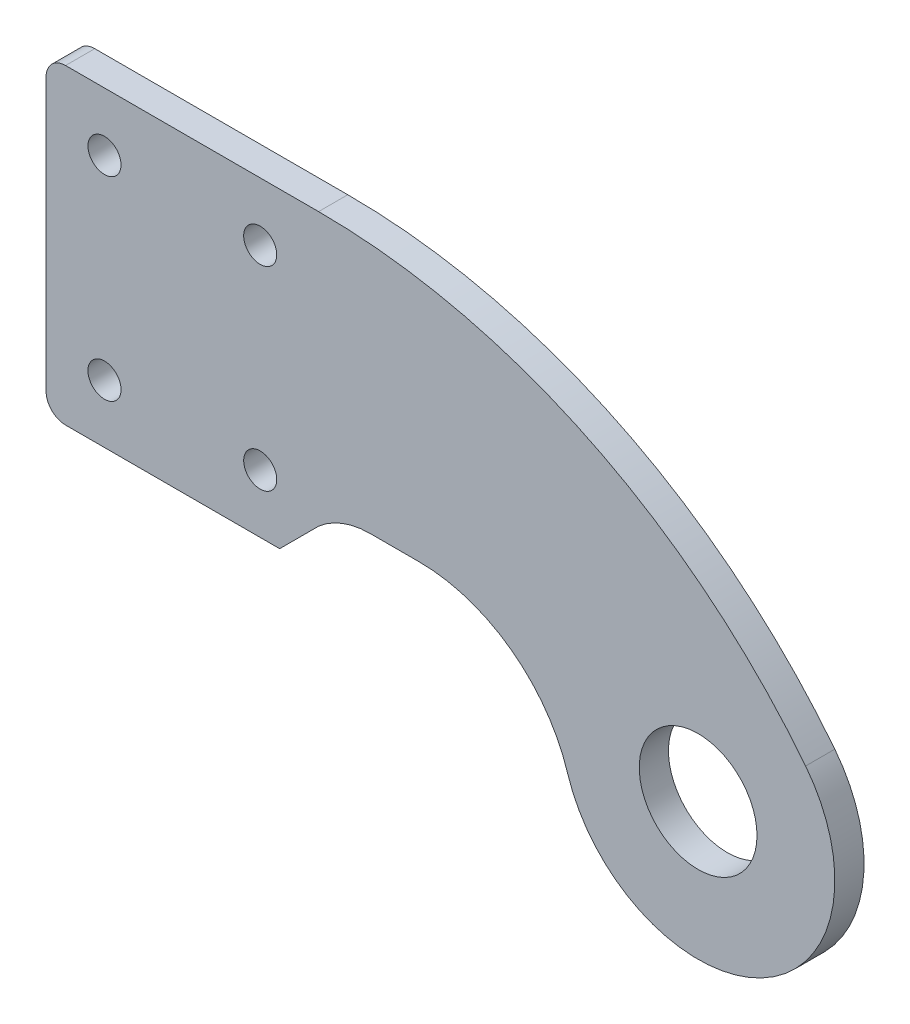
SolidWorks part; units mm, degrees
material "Hexcel AS4C (3000 Filaments)"
ref_plane "Plan de face" through (0, 0, 0) normal (0, 0, 1) x (1, 0, 0)
ref_plane "Plan de dessus" through (0, 0, 0) normal (0, 1, 0) x (1, 0, 0)
ref_plane "Plan de droite" through (0, 0, 0) normal (1, 0, 0) x (0, 0, -1)
sketch "Esquisse1" plane through (0, 0, 0) normal (0, 0, 1) x (1, 0, 0)
  line L0 (-19.5, 16.5) -> (2.8879, 6.4039) construction
  line L1 (-30.5, 13.5) -> (-22.5, 13.5) construction
  line L2 (-30.5, 13.5) -> (-30.5, 3.5) construction
  line L3 (-30.5, 3.5) -> (-22.5, 3.5) construction
  line L4 (-22.5, 13.5) -> (-22.5, 3.5) construction
  line L5 (-33.5, 16.5) -> (-19.5, 16.5)
  line L6 (-33.5, 16.5) -> (-33.5, 0.5)
  line L7 (-33.5, 0.5) -> (-19.5, 0.5)
  line L8 (-19.5, 16.5) -> (-19.5, 0.5) construction
  line L9 (-19.5, 0.5) -> (-19.5, 4.475) construction
  line L10 (-19.5, 4.475) -> (-5.4153, 4.475) construction
  line L11 (-19.5, 0.5) -> (-7.0072, 0.5)
  circle A0 centre (0, 0) radius 3.025
  circle A1 centre (0, 0) radius 7.025 construction
  circle A2 centre (-30.5, 13.5) radius 0.85
  circle A3 centre (-22.5, 13.5) radius 0.85
  circle A4 centre (-22.5, 3.5) radius 0.85
  circle A5 centre (-30.5, 3.5) radius 0.85
  arc A6 (-5.4153, 4.475) -> (2.8879, 6.4039) centre (0, 0) ccw construction
  arc A7 (-7.0072, 0.5) -> (5.5229, 4.3414) centre (0, 0) ccw
  arc A8 (-19.5, 16.5) -> (5.5229, 4.3414) centre (-19.5, -15.3285) cw
  dimension "D1" = 8
  dimension "D8" = 14.05
  dimension "D9" = 6.05
  dimension "D10" = 1.7
  dimension "D11" = 1.7
  dimension "D12" = 1.7
  dimension "D13" = 1.7
  dimension "D2" = 10
  dimension "D3" = 3
  dimension "D4" = 14
  dimension "D5" = 3
  dimension "D6" = 16
  dimension "D7" = 0.5
  dimension "D14" = 3.975
  dimension "D15" = 33.5
extrude "Boss.-Extru.1" add sketch "Esquisse1" along normal mid plane 1.5
fillet "Congé2" radius 1 2 edges at (-33.5, 0.5, 0) (-33.5, 16.5, 0)
sketch "Esquisse2" plane through (0, 0, 0.75) normal (0, 0, 1) x (1, 0, 0)
  line L0 (-33.5, 15.5) -> (-33.5, 1.5) construction
  line L2 (-19.5, 3.5) -> (-7.0072, 3.5)
  line L3 (-19.5, 3.5) -> (-19.5, 0.5)
  line L4 (-19.5, 0.5) -> (-7.0072, 0.5)
  line L6 (-7.0072, 3.5) -> (-7.0072, 0.5)
  dimension "D1" = 3
  dimension "D2" = 14
extrude "Enlèv. mat.-Extru.1" cut sketch "Esquisse2" against normal through all
chamfer "Chanfrein1" distance 2 angle 45 1 edges at (-19.5, 0.5, 0)
fillet "Congé3" radius 4 1 edges at (-19.5, 3.5, 0)
fillet "Congé4" radius 8 1 edges at (-7.0072, 3.5, 0)
